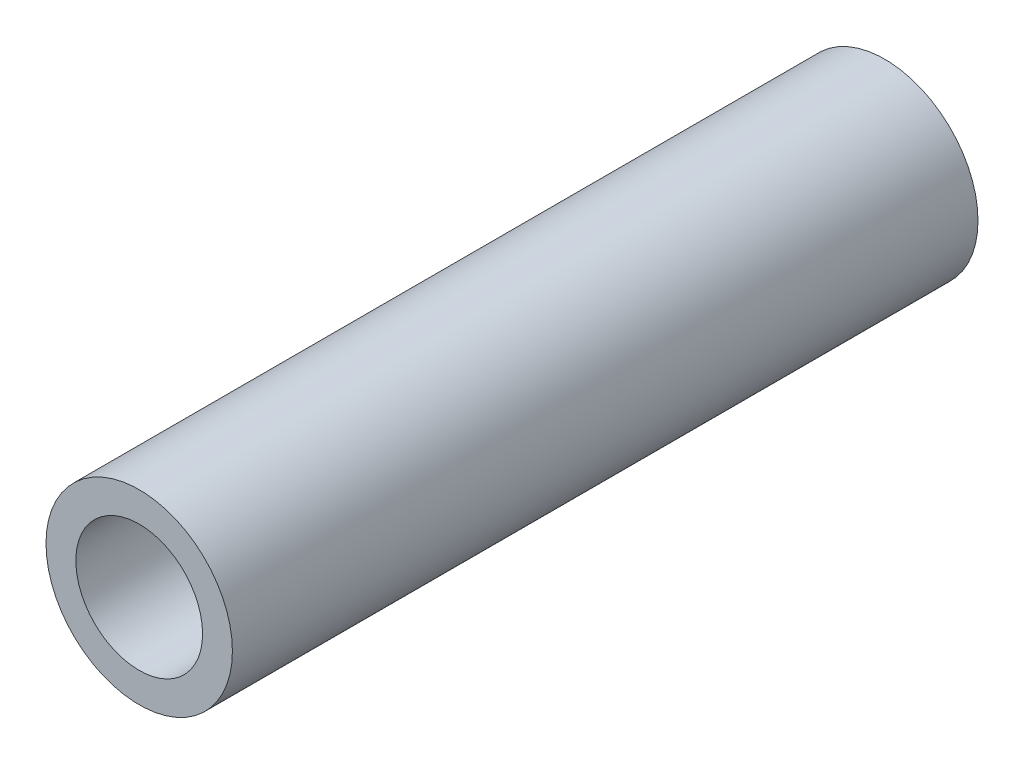
SolidWorks part; units mm, degrees
material "6061 Alloy"
ref_plane "Front Plane" through (0, 0, 0) normal (0, 0, 1) x (1, 0, 0)
ref_plane "Top Plane" through (0, 0, 0) normal (0, 1, 0) x (1, 0, 0)
ref_plane "Right Plane" through (0, 0, 0) normal (1, 0, 0) x (0, 0, -1)
sketch "Sketch1" plane through (0, 0, 0) normal (0, 0, 1) x (1, 0, 0)
  circle A0 centre (0, 0) radius 2.5
  dimension "D1" = 5
extrude "Boss-Extrude1" add sketch "Sketch1" along normal blind 20 contours A0
hole_wizard "M3 Clearance Hole1" positions "Sketch2" profile "Sketch3" hole size "M3" standard "ANSI Metric" end condition through all
sketch "Sketch2" plane through (0, 0, 20) normal (0, 0, 1) x (1, 0, 0)
  point P0 (0, 0)
sketch "Sketch3" plane through (0, 0, 20) normal (1, 0, 0) x (0, -1, 0)
  line L0 (0, 0) -> (0, 20)
  line L1 (0, 20) -> (1.7, 20)
  line L2 (1.7, 20) -> (1.7, 0)
  line L5 (1.7, 0) -> (0, 0)
  line L11 (0, -6.35) -> (0, 107.95) construction
  dimension "Thru Hole Dia." = 3.4
  dimension "Thru Hole Depth" = 20
